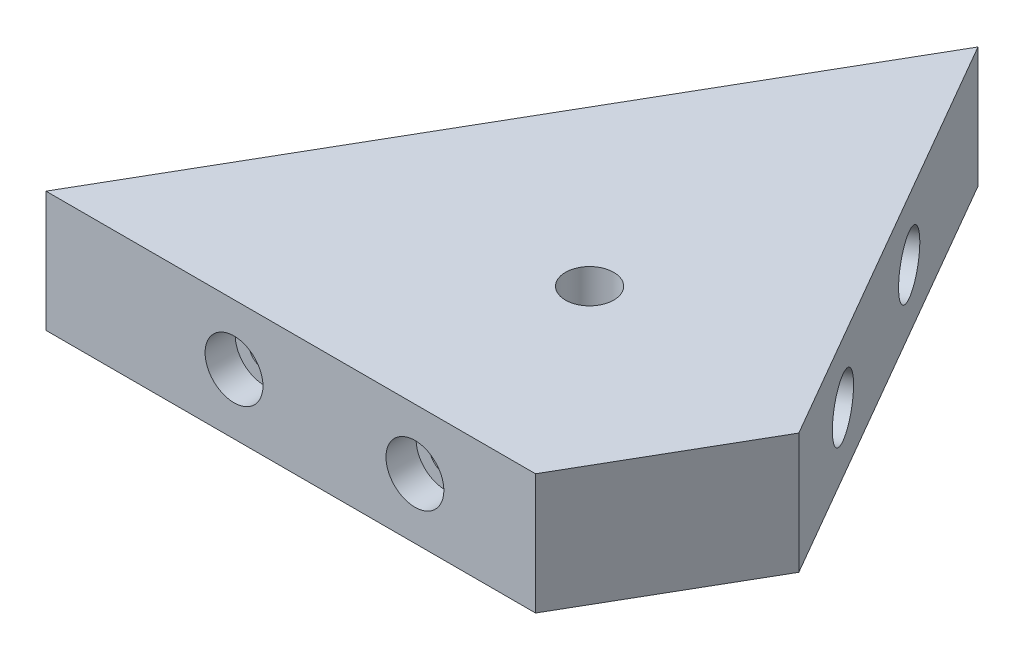
SolidWorks part; units mm, degrees
material "1023 Carbon Steel Sheet (SS)"
ref_plane "Front Plane" through (0, 0, 0) normal (0, 0, 1) x (1, 0, 0)
ref_plane "Top Plane" through (0, 0, 0) normal (0, 1, 0) x (1, 0, 0)
ref_plane "Right Plane" through (0, 0, 0) normal (1, 0, 0) x (0, 0, -1)
sketch "Sketch1" plane through (0, 0, 0) normal (0, 1, 0) x (1, 0, 0)
  line L0 (159.6594, -241.1624) -> (-297.5406, 22.8022) construction
  line L1 (-145.1406, 286.7667) -> (-449.9406, -241.1624) construction
  line L2 (-449.9406, -241.1624) -> (159.6594, -241.1624) construction
  line L3 (159.6594, -241.1624) -> (-145.1406, 286.7667) construction
  line L4 (93.6683, -241.1624) -> (93.6683, -203.0624) construction
  line L5 (119.0683, -241.1624) -> (129.2161, -223.5859)
  line L6 (55.5683, -241.1624) -> (55.5683, -181.0653) construction
  line L7 (15.9736, -241.1624) -> (51.8951, -178.9446)
  line L8 (15.9736, -241.1624) -> (119.0683, -241.1624)
  line L9 (51.8951, -178.9446) -> (129.2161, -223.5859)
  line L10 (93.6683, -203.0624) -> (55.5683, -203.0624) construction
  dimension "D1" = 609.6
  dimension "D2" = 38.1
  dimension "D3" = 25.4
  dimension "D4" = 38.1
  dimension "D6" = 40.5911
  dimension "D5" = 15.24
  dimension "D7" = 103.0947
  dimension "D8" = 60
  dimension "D9" = 120
extrude "Boss-Extrude1" add sketch "Sketch1" along normal blind 25.4
sketch "Sketch2" plane through (0, 0, 241.1624) normal (0, 0, 1) x (1, 0, 0)
  line L0 (15.9736, 0) -> (119.0683, 0) construction
  line L1 (15.9736, 0) -> (15.9736, 25.4) construction
  line L2 (119.0683, 0) -> (119.0683, 25.4) construction
  line L3 (15.9736, 25.4) -> (119.0683, 25.4) construction
  line L4 (15.9736, 0) -> (119.0683, 25.4) construction
  line L5 (119.0683, 0) -> (15.9736, 25.4) construction
  line L6 (93.6683, 25.4) -> (93.6683, 0) construction
  line L7 (55.5683, 0) -> (55.5683, 25.4) construction
  circle A0 centre (55.5683, 12.7) radius 6.096
  circle A1 centre (93.6683, 12.7) radius 6.096
  point P6 (67.521, 12.7)
  dimension "D4" = 12.192
  dimension "D5" = 12.192
  dimension "D1" = 25.4
  dimension "D2" = 25.4
  dimension "D3" = 38.1
extrude "Cut-Extrude1" cut sketch "Sketch2" against normal blind 6.35
sketch "Sketch3" plane through (0, 0, 234.8124) normal (0, 0, 1) x (1, 0, 0)
  circle A0 centre (55.5683, 12.7) radius 3.2639
  dimension "D1" = 6.5278
extrude "Cut-Extrude2" cut sketch "Sketch3" against normal blind 16.51
sketch "Sketch4" plane through (0, 0, 234.8124) normal (0, 0, 1) x (1, 0, 0)
  circle A0 centre (93.6683, 12.7) radius 3.2639
  dimension "D1" = 6.5278
extrude "Cut-Extrude3" cut sketch "Sketch4" against normal blind 16.51
mirror "Mirror1" about plane through (51.8951, 25.4, 178.9446) normal (-0.5, 0, 0.866) of "Boss-Extrude1", "Cut-Extrude1", "Cut-Extrude2", "Cut-Extrude3"
sketch "Sketch5" plane through (0, 25.4, 0) normal (0, 1, 0) x (1, 0, 0)
  line L0 (87.8165, -116.7268) -> (15.9736, -241.1624) construction
  line L1 (15.9736, -241.1624) -> (119.0683, -241.1624) construction
  line L2 (119.0683, -241.1624) -> (139.3639, -206.0094) construction
  line L3 (139.3639, -206.0094) -> (87.8165, -116.7268) construction
  line L4 (51.8951, -178.9446) -> (129.2161, -223.5859) construction
  circle A0 centre (90.5556, -201.2653) radius 5.08
  dimension "D1" = 10.16
  dimension "D2" = 44.6413
  dimension "D3" = 71.8429
extrude "Cut-Extrude4" cut sketch "Sketch5" against normal through all
ref_plane "Plane1" through (0, 0, 241.1624) normal (0, 0, 1) x (1, 0, 0)
equation "\"bplate_length\"= 24in"
equation "\"bplate_height\"= 6in"
equation "\"bplate_thickness\"= 0.5in"
equation "\"connector_plate_hole_diameter\"= 0.375in"
equation "\"connector_plate_hole_depth\"= 1in"
equation "\"connector_plate_thickness\"= 1in"
equation "\"D1@Sketch1\"=\"bplate_length\""
